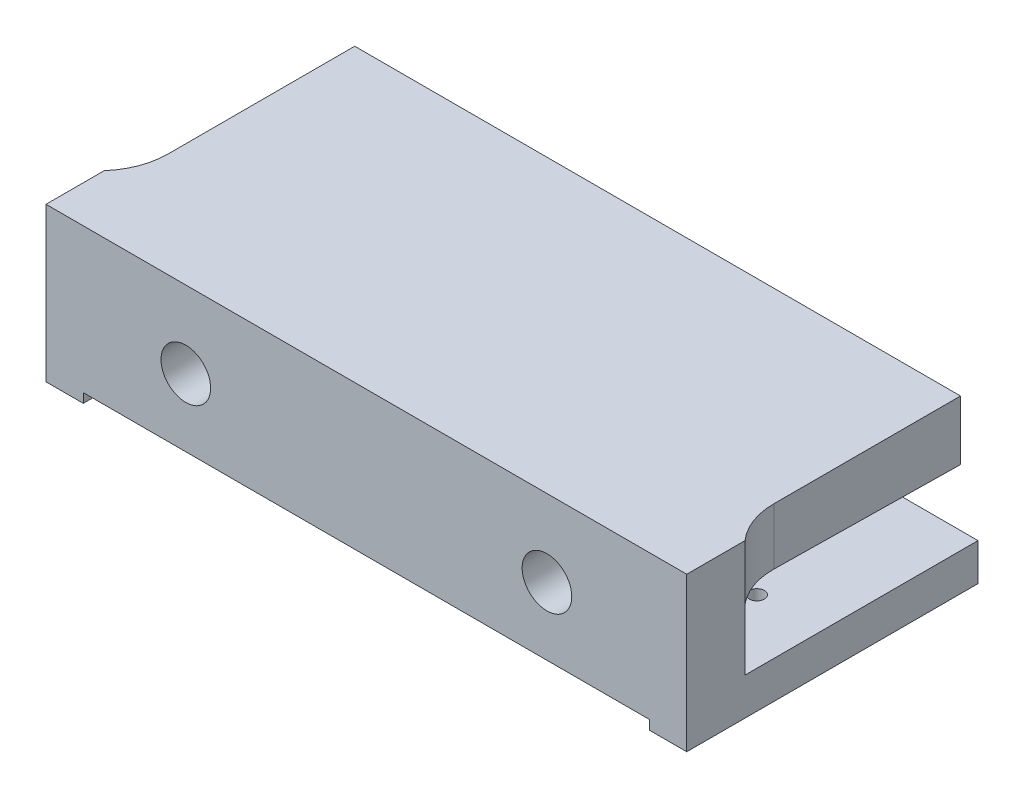
SolidWorks part; units mm, degrees
ref_plane "Front Plane" through (0, 0, 0) normal (0, 0, 1) x (1, 0, 0)
ref_plane "Top Plane" through (0, 0, 0) normal (0, 1, 0) x (1, 0, 0)
ref_plane "Right Plane" through (0, 0, 0) normal (1, 0, 0) x (0, 0, -1)
sketch "Sketch1" plane through (0, 0, 0) normal (0, 1, 0) x (1, 0, 0)
  line L1 (-34.925, -15.875) -> (34.925, -15.875)
  line L2 (-34.925, -15.875) -> (-34.925, 15.875)
  line L3 (-34.925, 15.875) -> (34.925, 15.875)
  line L4 (34.925, -15.875) -> (34.925, 15.875)
  line L5 (-34.925, -15.875) -> (34.925, 15.875) construction
  line L6 (-34.925, 15.875) -> (34.925, -15.875) construction
  point P0 (0, 0)
  dimension "D1" = 31.75
  dimension "D2" = 69.85
extrude "Boss-Extrude1" add sketch "Sketch1" along normal blind 16.764
sketch "Sketch2" plane through (-34.925, 0, 0) normal (-1, 0, 0) x (0, 0, 1)
  line L0 (-15.875, 16.764) -> (-15.875, 0) construction
  line L1 (-15.875, 10.414) -> (9.525, 10.414)
  line L2 (-15.875, 10.414) -> (-15.875, 4.064)
  line L3 (-15.875, 4.064) -> (9.525, 4.064)
  line L4 (9.525, 10.414) -> (9.525, 4.064)
  dimension "D1" = 6.35
  dimension "D2" = 25.4
  dimension "D3" = 4.064
extrude "Cut-Extrude1" cut sketch "Sketch2" against normal up to surface (69.85 mm away) up to face at (34.925, 8.382, 0)
sketch "Sketch3" plane through (-34.925, 0, 0) normal (-1, 0, 0) x (0, 0, 1)
  line L0 (9.525, 10.414) -> (-15.875, 10.414) construction
  line L1 (-15.875, 16.764) -> (9.525, 16.764)
  line L2 (-15.875, 16.764) -> (-15.875, 10.414)
  line L3 (-15.875, 10.414) -> (9.525, 10.414)
  line L4 (9.525, 16.764) -> (9.525, 10.414)
  dimension "D1" = 25.4
extrude "Cut-Extrude2" cut sketch "Sketch3" against normal blind 50.8
mirror "Mirror1" about plane through (0, 0, 0) normal (1, 0, 0) of "Cut-Extrude2"
sketch "Sketch5" plane through (0, 0, 0) normal (0, -1, 0) x (1, 0, 0)
  line L0 (-27.9908, 1.2954) -> (27.9908, 1.2954) construction
  line L1 (-34.925, 15.875) -> (34.925, 15.875) construction
  line L3 (-30.861, 15.875) -> (30.861, 15.875)
  line L4 (-30.861, 15.875) -> (-30.861, -1.2446)
  line L5 (-30.861, -1.2446) -> (30.861, -1.2446)
  line L6 (30.861, 15.875) -> (30.861, -1.2446)
  circle A0 centre (-27.9908, 1.2954) radius 0.8192
  circle A1 centre (27.9908, 1.2954) radius 0.8192
  point P0 (-27.9908, 1.2954)
  point P1 (27.9908, 1.2954)
  point P2 (0, 1.2954)
  point P12 (0, -1.2446)
  point P18 (0, -1.2446)
  line M3 (34.925, 15.875) -> (-34.925, 15.875)
  dimension "D5" = 1.6383
  dimension "D6" = 1.6383
  dimension "D1" = 2.54
  dimension "D2" = 55.9816
  dimension "D3" = 17.1196
  dimension "D4" = 61.722
extrude "Cut-Extrude3" cut sketch "Sketch5" against normal blind 1.016 contours L6 L4 L5 A0 A1 M3 | A0 | A1 region at (0, 0, 7.3393) region at (-27.9908, 0, 1.2954) region at (27.9908, 0, 1.2954)
extrude "Cut-Extrude4" cut sketch "Sketch5<3>" against normal through all contours A0 | A1 region at (-27.9908, 0, 1.2954) region at (27.9908, 0, 1.2954)
sketch "Sketch5<3>" plane through (0, 0, 0) normal (0, -1, 0) x (1, 0, 0) same geometry as "Sketch5"
sketch "Sketch7" plane through (0, 0, 9.525) normal (0, 0, -1) x (-1, 0, 0)
  line L0 (-34.925, 16.764) -> (34.925, 16.764) construction
  line L1 (-34.925, 9.144) -> (34.925, 9.144)
  line L2 (-34.925, 9.144) -> (-34.925, 16.764)
  line L3 (-34.925, 16.764) -> (34.925, 16.764)
  line L4 (34.925, 9.144) -> (34.925, 16.764)
  line L5 (-34.925, 9.144) -> (34.925, 16.764) construction
  line L6 (-34.925, 16.764) -> (34.925, 9.144) construction
  line L7 (-34.925, 4.064) -> (34.925, 4.064) construction
  point P0 (0, 12.954)
  dimension "D1" = 5.08
  dimension "D2" = 69.85
extrude "Boss-Extrude2" add sketch "Sketch7" along normal blind 25.4
sketch "Sketch8" plane through (-34.925, 0, 0) normal (-1, 0, 0) x (0, 0, 1)
  line L0 (-15.875, 10.287) -> (9.525, 10.668)
  line L1 (-15.875, 9.144) -> (-15.875, 16.764) construction
  line L3 (-15.875, 9.144) -> (9.525, 9.144) construction
  line L5 (9.525, 9.144) -> (9.525, 4.064) construction
  line L6 (-15.875, 10.287) -> (-15.875, 9.144)
  line L7 (-15.875, 9.144) -> (9.525, 9.144)
  line L8 (9.525, 9.144) -> (9.525, 10.668)
  dimension "D1" = 1.143
  dimension "D2" = 1.524
extrude "Cut-Extrude9" cut sketch "Sketch8" against normal through all both and the other way through all
sketch "Sketch13" plane through (0, 0, 15.875) normal (0, 0, 1) x (1, 0, 0)
  line L0 (-19.685, 8.382) -> (19.685, 8.382) construction
  line L2 (34.925, 16.764) -> (-34.925, 0) construction
  circle A0 centre (-19.685, 8.382) radius 2.7051
  circle A1 centre (19.685, 8.382) radius 2.7051
  point P4 (0, 8.382)
  point P5 (0, 8.382)
  dimension "D2" = 5.4102
  dimension "D3" = 5.4102
  dimension "D1" = 39.37
extrude "Cut-Extrude12" cut sketch "Sketch13" against normal blind 4.064
sketch "Sketch16" plane through (0, 0, 15.875) normal (0, 0, 1) x (1, 0, 0)
  line L0 (-13.4811, 16.764) -> (13.4811, 16.764)
  line L1 (-13.4811, 16.764) -> (-13.481, 2.1717)
  line L2 (-13.481, 2.1717) -> (13.481, 2.1717)
  line L3 (13.4811, 16.764) -> (13.481, 2.1717)
  line L4 (-11.2459, 14.859) -> (12.3635, 14.859) construction
  line L5 (-11.2459, 14.859) -> (-11.2459, 7.8867) construction
  line L6 (-11.2459, 7.8867) -> (12.3635, 7.8867) construction
  line L7 (12.3635, 14.859) -> (12.3635, 7.8867) construction
  line L8 (13.4811, 16.764) -> (3.3211, 16.764)
  line L9 (13.4811, 16.764) -> (13.4811, 11.684)
  line L10 (13.4811, 11.684) -> (3.3211, 11.684)
  line L11 (3.3211, 16.764) -> (3.3211, 11.684)
  line L12 (-13.481, 2.1717) -> (-3.321, 2.1717)
  line L13 (-13.481, 2.1717) -> (-13.481, 9.1567)
  line L14 (-13.481, 9.1567) -> (-3.321, 9.1567)
  line L15 (-3.321, 2.1717) -> (-3.321, 9.1567)
  line L16 (-34.925, 16.764) -> (34.925, 16.764) construction
  circle A0 centre (-11.2459, 14.859) radius 0.8255
  circle A1 centre (12.3635, 14.859) radius 0.8255
  circle A2 centre (12.3635, 7.8867) radius 0.8255
  circle A3 centre (-11.2459, 7.8867) radius 0.8255
  point P18 (0, 16.764)
  point P21 (0, 16.764)
  dimension "D7" = 1.651
  dimension "D8" = 1.651
  dimension "D9" = 1.651
  dimension "D10" = 1.651
  dimension "D1" = 26.9621
  dimension "D2" = 14.5923
  dimension "D3" = 2.2352
  dimension "D4" = 1.1176
  dimension "D5" = 1.905
  dimension "D6" = 5.715
  dimension "D11" = 10.16
  dimension "D12" = 5.08
  dimension "D13" = 10.16
  dimension "D14" = 6.985
sketch "Sketch17" plane through (0, 0, -15.875) normal (0, 0, -1) x (-1, 0, 0)
  line L0 (34.925, 16.764) -> (-34.925, 16.764) construction
  line L1 (-33.02, 16.764) -> (33.02, 16.764)
  line L2 (-33.02, 16.764) -> (-33.02, 10.287)
  line L3 (-33.02, 10.287) -> (33.02, 10.287)
  line L4 (33.02, 16.764) -> (33.02, 10.287)
  line L5 (-34.925, 10.287) -> (34.925, 10.287) construction
  line L7 (-33.02, 16.764) -> (-34.925, 16.764)
  line L8 (-33.02, 16.764) -> (-33.02, 10.287)
  line L9 (-33.02, 10.287) -> (-34.925, 10.287)
  line L10 (-34.925, 16.764) -> (-34.925, 10.287)
  line L11 (33.02, 16.764) -> (34.925, 16.764)
  line L12 (33.02, 16.764) -> (33.02, 10.287)
  line L13 (33.02, 10.287) -> (34.925, 10.287)
  line L14 (34.925, 16.764) -> (34.925, 10.287)
  point P13 (0, 16.764)
  line M4 (-34.925, 16.764) -> (-34.925, 10.287)
  line M5 (-34.925, 10.287) -> (34.925, 10.287)
  line M6 (34.925, 10.287) -> (34.925, 16.764)
  line M7 (34.925, 16.764) -> (-34.925, 16.764)
  dimension "D1" = 66.04
extrude "Cut-Extrude13" cut sketch "Sketch17" against normal up to surface (25.4 mm away) contours L2 M7 M4 M5 | L4 M7 M5 M6 region at (33.9725, 13.5255, -15.875) region at (-33.9725, 13.5255, -15.875) up to face at (0, 7.366, 9.525)
fillet "Fillet1" radius 7.62 2 edges at (-33.02, 13.716, 9.525) (33.02, 13.716, 9.525)
